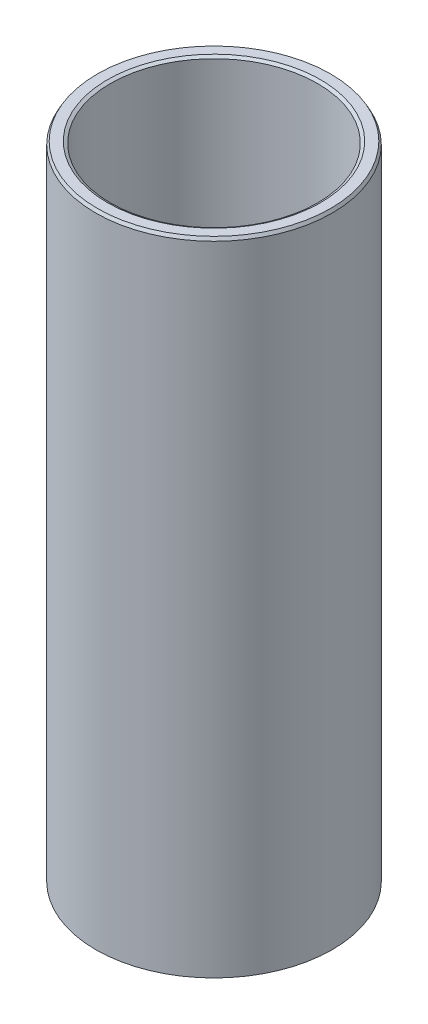
SolidWorks part; units mm, degrees
ref_plane "Front Plane" through (0, 0, 0) normal (0, 0, 1) x (1, 0, 0)
ref_plane "Top Plane" through (0, 0, 0) normal (0, 1, 0) x (1, 0, 0)
ref_plane "Right Plane" through (0, 0, 0) normal (1, 0, 0) x (0, 0, -1)
sketch "Sketch1" plane through (0, 0, 0) normal (0, 1, 0) x (1, 0, 0)
  circle A0 centre (0, 0) radius 42.5
  dimension "SLEEVE_OD" = 85
extrude "Boss-Extrude1" add sketch "Sketch1" along normal blind 230.8846
sketch "Sketch2" plane through (0, 0, 0) normal (0, 1, 0) x (1, 0, 0)
  circle A0 centre (0, 0) radius 37.1834
  dimension "BORE_D" = 74.3668
extrude "Cut-Extrude1" cut sketch "Sketch2" along normal through all
chamfer "Chamfer1" distance 1.0977 angle 29.769 4 edges at (0, 230.8846, 37.1834) (0, 0, 37.1834) (0, 0, 42.5) (0, 230.8846, 42.5) first distance on face at (0, 230.8846, 37.1834) first distance on face at (0, 0, 37.1834) first distance on face at (0, 230.8846, 42.5)
